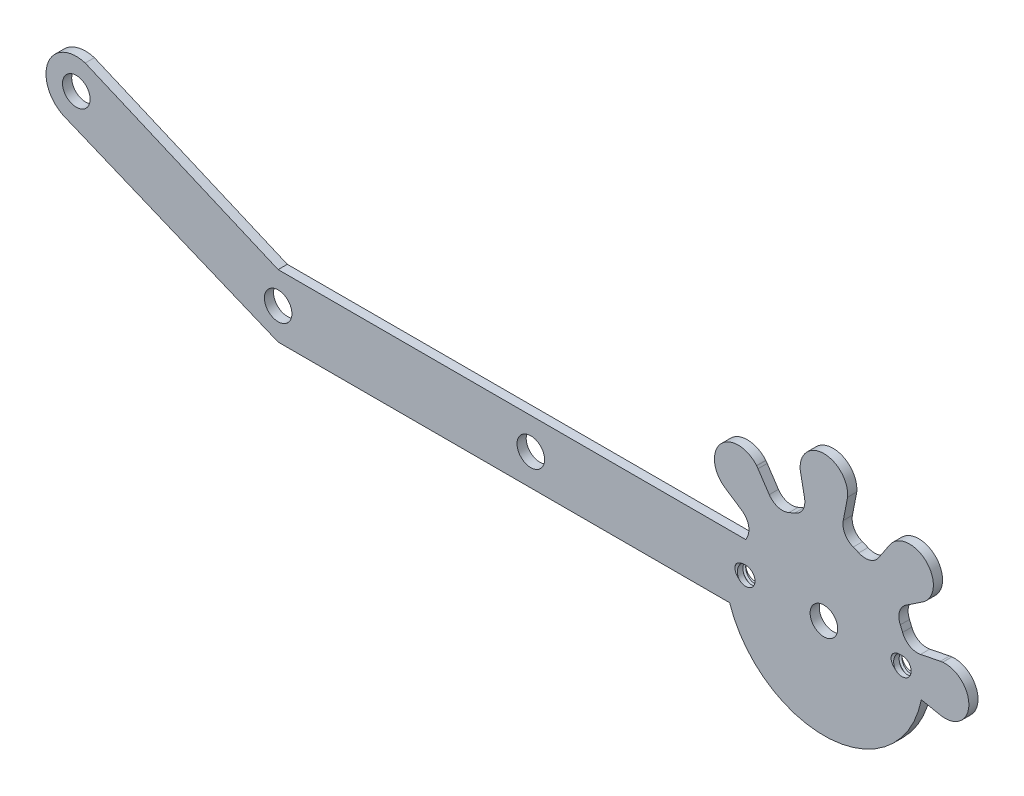
SolidWorks part; units mm, degrees
ref_plane "Alzado" through (0, 0, 0) normal (0, 0, 1) x (1, 0, 0)
ref_plane "Planta" through (0, 0, 0) normal (0, 1, 0) x (1, 0, 0)
ref_plane "Vista lateral" through (0, 0, 0) normal (1, 0, 0) x (0, 0, -1)
sketch "Model" plane through (0, 0, 0) normal (0, 0, 1) x (1, 0, 0)
  line L0 (64.9205, 22.666) -> (65.3921, 25.0947)
  line L1 (60.2353, 25.0947) -> (60.7069, 22.666)
  line L2 (59.6178, 20.7097) -> (59.0174, 20.461)
  line L3 (56.864, 21.0742) -> (55.6436, 22.9057)
  line L4 (55.5011, 23.0994) -> (55.4801, 23.125)
  line L5 (51.8337, 19.4786) -> (51.8593, 19.4576)
  line L6 (52.053, 19.3151) -> (53.8845, 18.0947)
  line L7 (54.3342, 15.5605) -> (30.9137, 15.5605)
  line L8 (30.9137, 15.5605) -> (3.4137, 15.5605)
  line L9 (3.4137, 15.5605) -> (-17.587, 24.5348)
  line L10 (-19.7197, 18.2925) -> (3.4137, 8.7295)
  line L11 (3.4137, 8.7295) -> (30.9137, 8.7295)
  line L12 (30.9137, 8.7295) -> (52.5514, 8.7295)
  line L13 (73.4189, 10.0213) -> (75.4928, 9.606)
  line L14 (75.7305, 9.5698) -> (75.7635, 9.5666)
  line L15 (75.7635, 14.7234) -> (75.7305, 14.7201)
  line L16 (75.4928, 14.6839) -> (73.3347, 14.2518)
  line L17 (71.7429, 18.0947) -> (73.5745, 19.3151)
  line L18 (73.7682, 19.4576) -> (73.7938, 19.4786)
  line L19 (70.1474, 23.125) -> (70.1263, 23.0994)
  line L20 (69.9839, 22.9057) -> (68.7635, 21.0742)
  circle A0 centre (62.8137, 12.145) radius 1.5
  arc A1 (65.3921, 25.0947) -> (60.2353, 25.0947) centre (62.8137, 25.3324) ccw
  arc A2 (59.6178, 20.7097) -> (60.7069, 22.666) centre (59.0143, 22.327) ccw
  arc A3 (56.864, 21.0742) -> (59.0174, 20.461) centre (58.3005, 22.0314) ccw
  arc A4 (55.6436, 22.9057) -> (55.5011, 23.0994) centre (53.4888, 21.4699) ccw
  arc A5 (55.4801, 23.125) -> (51.8337, 19.4786) centre (53.4888, 21.4699) ccw
  arc A6 (51.8593, 19.4576) -> (52.053, 19.3151) centre (53.4888, 21.4699) ccw
  arc A7 (54.4977, 15.9413) -> (53.8845, 18.0947) centre (52.9273, 16.6582) ccw
  arc A8 (54.4977, 15.9413) -> (54.3342, 15.5605) centre (62.8137, 12.145) ccw
  arc A9 (-17.587, 24.5348) -> (-19.7197, 18.2925) centre (-18.5533, 21.3795) ccw
  arc A10 (52.5514, 8.7295) -> (73.4189, 10.0213) centre (62.8137, 12.145) ccw
  arc A11 (75.4928, 9.606) -> (75.7305, 9.5698) centre (76.0012, 12.145) ccw
  arc A12 (75.7635, 9.5666) -> (75.7635, 14.7234) centre (76.0012, 12.145) ccw
  arc A13 (75.7305, 14.7201) -> (75.4928, 14.6839) centre (76.0012, 12.145) ccw
  arc A14 (71.3785, 15.3409) -> (73.3347, 14.2518) centre (72.9958, 15.9444) ccw
  arc A15 (71.3785, 15.3409) -> (71.1298, 15.9413) centre (62.8137, 12.145) ccw
  arc A16 (71.7429, 18.0947) -> (71.1298, 15.9413) centre (72.7001, 16.6582) ccw
  arc A17 (73.5745, 19.3151) -> (73.7682, 19.4576) centre (72.1387, 21.4699) ccw
  arc A18 (73.7938, 19.4786) -> (70.1474, 23.125) centre (72.1387, 21.4699) ccw
  arc A19 (70.1263, 23.0994) -> (69.9839, 22.9057) centre (72.1387, 21.4699) ccw
  arc A20 (66.61, 20.461) -> (68.7635, 21.0742) centre (67.3269, 22.0314) ccw
  arc A21 (66.61, 20.461) -> (66.0097, 20.7097) centre (62.8137, 12.145) ccw
  arc A22 (64.9205, 22.666) -> (66.0097, 20.7097) centre (66.6132, 22.327) ccw
  circle A23 centre (30.9137, 12.145) radius 1.5
  circle A24 centre (3.4137, 12.145) radius 1.5
  circle A25 centre (-18.5533, 21.3795) radius 1.5
  circle A29 centre (54.3137, 12.145) radius 1
  circle A33 centre (71.3137, 12.145) radius 1
  point P82 (62.8137, 12.145)
extrude "Saliente-Extruir1" add sketch "Model" along normal blind 1
thread "Rosca1" pitch 0.4 method cut profile "Perfil de rosca1" start angle 0, offset 2, length 10, pitch 0.9, diameter 2
ref_plane "Plano1" through (70.3137, 12.145, 3) normal (0, -1, 0) x (-1, 0, 0)
sketch "Perfil de rosca1" plane through (70.3137, 12.145, 3) normal (0, -1, 0) x (-1, 0, 0)
  line L0 (0, 0) -> (0, 0.4) construction
  line L1 (0, 0) -> (0.2165, 0.125)
  line L2 (0.2165, 0.125) -> (0.2165, 0.175)
  line L3 (0.2165, 0.175) -> (0, 0.3)
  line L4 (0.2165, 0.15) -> (0, 0.15) construction
  line L11 (0, 0) -> (0, 0.3)
  point P2 (0, 0)
  dimension "Pitch" = 0.4
  dimension "Profile_Angle" = 60
  dimension "Profile_Land" = 0.05
  dimension "Profile_Height" = 0.2165
thread "Rosca2" pitch 0.4 method cut profile "Perfil de rosca2" start angle 0, offset 2, length 10, pitch 0.9, diameter 2
ref_plane "Plano2" through (53.3137, 12.145, 3) normal (0, -1, 0) x (-1, 0, 0)
sketch "Perfil de rosca2" plane through (53.3137, 12.145, 3) normal (0, -1, 0) x (-1, 0, 0)
  line L0 (0, 0) -> (0, 0.4) construction
  line L1 (0, 0) -> (0.2165, 0.125)
  line L2 (0.2165, 0.125) -> (0.2165, 0.175)
  line L3 (0.2165, 0.175) -> (0, 0.3)
  line L4 (0.2165, 0.15) -> (0, 0.15) construction
  line L11 (0, 0) -> (0, 0.3)
  point P2 (0, 0)
  dimension "Pitch" = 0.4
  dimension "Profile_Angle" = 60
  dimension "Profile_Land" = 0.05
  dimension "Profile_Height" = 0.2165
